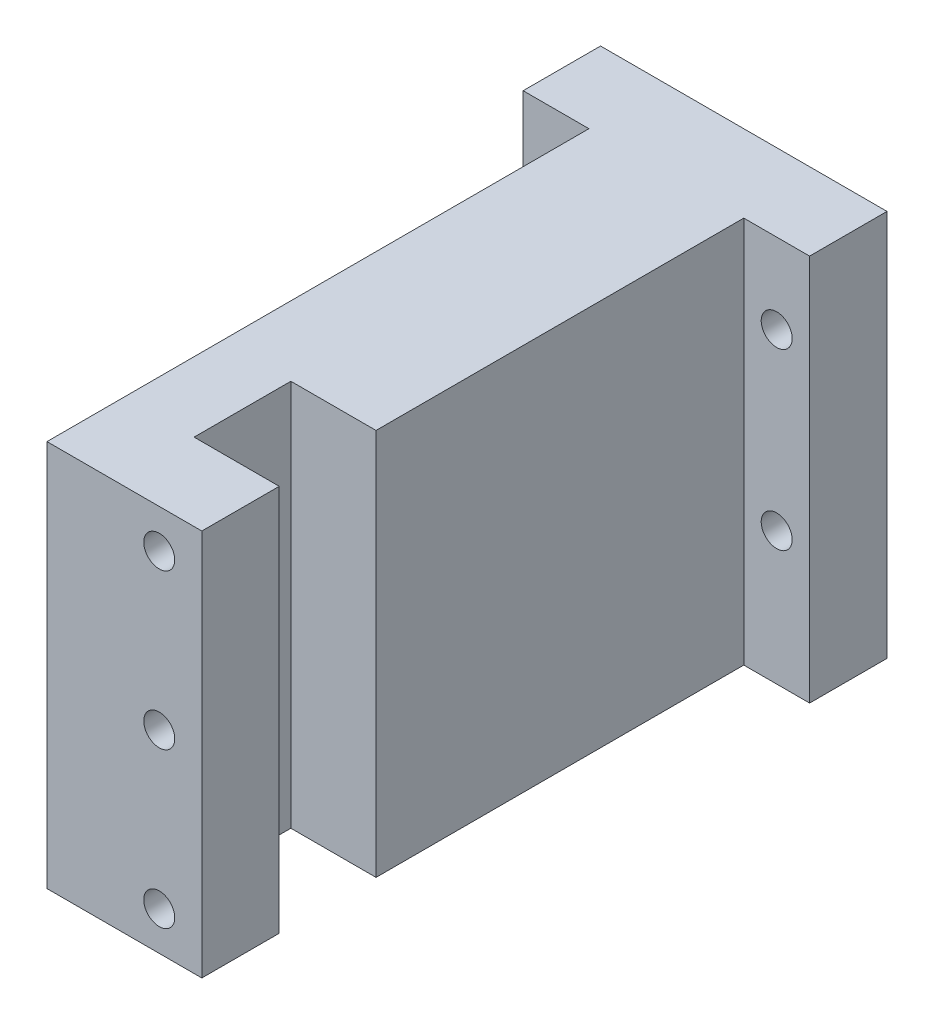
SolidWorks part; units mm, degrees
ref_plane "Płaszczyzna przednia" through (0, 0, 0) normal (0, 0, 1) x (1, 0, 0)
ref_plane "Płaszczyzna górna" through (0, 0, 0) normal (0, 1, 0) x (1, 0, 0)
ref_plane "Płaszczyzna prawa" through (0, 0, 0) normal (1, 0, 0) x (0, 0, -1)
sketch "Szkic1" plane through (0, 0, 0) normal (0, 0, 1) x (1, 0, 0)
  line L1 (-37.1341, 6.1884) -> (36.8659, 6.1884)
  line L2 (-37.1341, 6.1884) -> (-37.1341, -93.8116)
  line L3 (-37.1341, -93.8116) -> (36.8659, -93.8116)
  line L4 (36.8659, 6.1884) -> (36.8659, -93.8116)
  dimension "D2" = 100
extrude "Dodanie-wyciągnięcie1" add sketch "Szkic1" along normal blind 20
sketch "Szkic3" plane through (0, 0, 20) normal (0, 0, 1) x (1, 0, 0)
  line L0 (-37.1341, 6.1884) -> (-37.1341, -93.8116) construction
  line L4 (-20.1341, 6.1884) -> (-20.1341, -93.8116)
  line L5 (19.8659, -93.8116) -> (-20.1341, -93.8116)
  line L7 (19.8659, -93.8116) -> (19.8659, 6.1884)
  line L8 (19.8659, 6.1884) -> (-20.1341, 6.1884)
  line L10 (-37.1341, -93.8116) -> (36.8659, -93.8116) construction
  line L11 (-20.1341, -93.8116) -> (-20.1341, 6.1884)
  line L15 (19.8659, 6.1884) -> (19.8659, -93.8116)
  line L16 (36.8659, 6.1884) -> (-37.1341, 6.1884) construction
  line M4 (36.8659, 6.1884) -> (-37.1341, 6.1884)
  line M6 (-37.1341, -93.8116) -> (36.8659, -93.8116)
  dimension "D1" = 17
  dimension "D2" = 40
extrude "Dodanie-wyciągnięcie2" add sketch "Szkic3" along normal blind 140 contours L7 L4 M6 M4 region at (-0.1341, -43.8116, 20)
sketch "Szkic4" plane through (0, 0, 20) normal (0, 0, 1) x (1, 0, 0)
  line L0 (-37.1341, 6.1884) -> (-37.1341, -93.8116) construction
  line L1 (-20.1341, 6.1884) -> (-37.1341, 6.1884) construction
  circle A0 centre (-28.6341, -14.5116) radius 4
  dimension "D1" = 8.5
  dimension "D2" = 20.7
extrude "Wytnij-wyciągnięcie1" cut sketch "Szkic4" against normal blind 20
pattern_linear "Szyk liniowy1" count 2 spacing 45 along (0, -1, 0) count 2 spacing 57 along (1, 0, 0) of "Wytnij-wyciągnięcie1"
sketch "Szkic5" plane through (0, 6.1884, 0) normal (0, 1, 0) x (1, 0, 0)
  line L1 (-2.1341, -140) -> (19.8659, -140)
  line L2 (-2.1341, -140) -> (-2.1341, -115)
  line L3 (-2.1341, -115) -> (19.8659, -115)
  line L4 (19.8659, -140) -> (19.8659, -115)
  line L5 (19.8659, -160) -> (-20.1341, -160) construction
  line L6 (19.8659, -160) -> (19.8659, -20) construction
  point P4 (0, 0)
  point P8 (0, 0)
  dimension "D1" = 22
  dimension "D2" = 20
  dimension "D3" = 25
extrude "Wytnij-wyciągnięcie2" cut sketch "Szkic5" against normal blind 100
sketch "Szkic6" plane through (0, 0, 160) normal (0, 0, 1) x (1, 0, 0)
  line L0 (-20.1341, -93.8116) -> (19.8659, -93.8116) construction
  line L2 (19.8659, -93.8116) -> (19.8659, 6.1884) construction
  circle A0 centre (8.8659, -3.8116) radius 4
  circle A1 centre (8.8659, -43.8116) radius 4
  circle A2 centre (8.8659, -83.8116) radius 4
  dimension "D1" = 40
  dimension "D2" = 40
  dimension "D3" = 10
  dimension "D4" = 11
extrude "Wytnij-wyciągnięcie3" cut sketch "Szkic6" against normal blind 10
